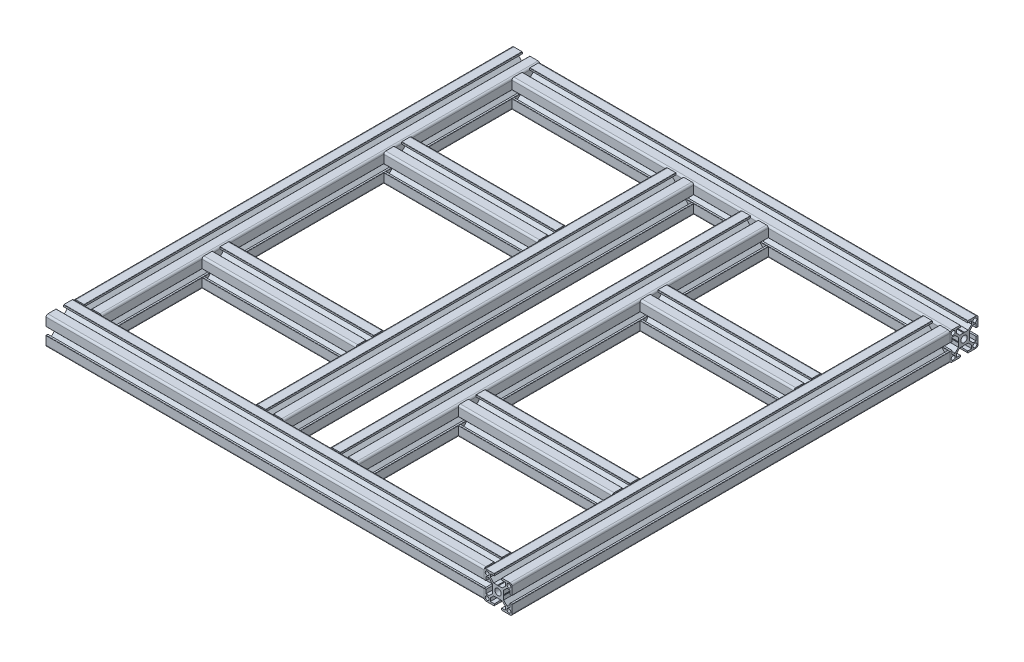
SolidWorks part; units mm, degrees
ref_plane "Front Plane" through (0, 0, 0) normal (0, 0, 1) x (1, 0, 0)
ref_plane "Top Plane" through (0, 0, 0) normal (0, 1, 0) x (1, 0, 0)
ref_plane "Right Plane" through (0, 0, 0) normal (1, 0, 0) x (0, 0, -1)
sketch "Sketch1" plane through (0, 0, 0) normal (0, 1, 0) x (1, 0, 0)
  line L0 (-40, 235) -> (-40, -235)
  line L1 (-235, 235) -> (235, 235)
  line L2 (-235, 235) -> (-235, -235)
  line L3 (-235, -235) -> (235, -235)
  line L4 (235, 235) -> (235, -235)
  line L5 (-235, 235) -> (235, -235) construction
  line L6 (-235, -235) -> (235, 235) construction
  line L7 (40, 235) -> (40, -235)
  line L8 (-235, 97.5) -> (-40, 97.5)
  line L9 (-235, -97.5) -> (-40, -97.5)
  line L11 (40, 97.5) -> (235, 97.5)
  line L14 (40, -97.5) -> (235, -97.5)
  point P0 (0, 0)
  point P15 (-235, 0)
  point P18 (0, 0)
  point P19 (0, 0)
  dimension "D1" = 470
  dimension "D2" = 195
  dimension "D3" = 195
  dimension "D4" = 97.5
  dimension "D5" = 195
other "30xs6 30X30S6(1)" corner treatment butt1
ref_plane "Plane1" through (-235, 0, -235) normal (1, 0, 0) x (0, 0, -1)
sketch "草图1" plane through (-235, 0, -235) normal (1, 0, 0) x (0, 0, -1)
  line L0 (-14.7, 4) -> (-13, 4)
  line L1 (-13, 4) -> (-13, 8.25)
  line L2 (-13, 8.25) -> (-9.6642, 8.25)
  line L3 (-9.6642, 8.25) -> (-6, 4.5858)
  line L4 (-6, 4.5858) -> (-6, 0.5196)
  line L5 (-6, 0.5196) -> (-5.7, 0)
  line L6 (-5.7, 0) -> (-6, -0.5196)
  line L7 (-6, -0.5196) -> (-6, -4.5858)
  line L8 (-6, -4.5858) -> (-9.6642, -8.25)
  line L9 (-9.6642, -8.25) -> (-13, -8.25)
  line L10 (-13, -8.25) -> (-13, -4)
  line L11 (-13, -4) -> (-14.7, -4)
  line L12 (-15, -4.3) -> (-15, -13)
  line L13 (-13, -15) -> (-4.3, -15)
  line L14 (-4, -14.7) -> (-4, -13)
  line L15 (-4, -13) -> (-8.25, -13)
  line L16 (-8.25, -13) -> (-8.25, -9.6642)
  line L17 (-8.25, -9.6642) -> (-4.5858, -6)
  line L18 (-4.5858, -6) -> (-0.5196, -6)
  line L19 (-0.5196, -6) -> (0, -5.7)
  line L20 (0, -5.7) -> (0.5196, -6)
  line L21 (0.5196, -6) -> (4.5858, -6)
  line L22 (4.5858, -6) -> (8.25, -9.6642)
  line L23 (8.25, -9.6642) -> (8.25, -13)
  line L24 (8.25, -13) -> (4, -13)
  line L25 (4, -13) -> (4, -14.7)
  line L26 (4.3, -15) -> (13, -15)
  line L27 (15, -13) -> (15, -4.3)
  line L28 (14.7, -4) -> (13, -4)
  line L29 (13, -4) -> (13, -8.25)
  line L30 (13, -8.25) -> (9.6642, -8.25)
  line L31 (9.6642, -8.25) -> (6, -4.5858)
  line L32 (6, -4.5858) -> (6, -0.5196)
  line L33 (6, -0.5196) -> (5.7, 0)
  line L34 (5.7, 0) -> (6, 0.5196)
  line L35 (6, 0.5196) -> (6, 4.5858)
  line L36 (6, 4.5858) -> (9.6642, 8.25)
  line L37 (9.6642, 8.25) -> (13, 8.25)
  line L38 (13, 8.25) -> (13, 4)
  line L39 (13, 4) -> (14.7, 4)
  line L40 (15, 4.3) -> (15, 13)
  line L41 (13, 15) -> (4.3, 15)
  line L42 (4, 14.7) -> (4, 13)
  line L43 (4, 13) -> (8.25, 13)
  line L44 (8.25, 13) -> (8.25, 9.6642)
  line L45 (8.25, 9.6642) -> (4.5858, 6)
  line L46 (4.5858, 6) -> (0.5196, 6)
  line L47 (0.5196, 6) -> (0, 5.7)
  line L48 (0, 5.7) -> (-0.5196, 6)
  line L49 (-0.5196, 6) -> (-4.5858, 6)
  line L50 (-4.5858, 6) -> (-8.25, 9.6642)
  line L51 (-8.25, 9.6642) -> (-8.25, 13)
  line L52 (-8.25, 13) -> (-4, 13)
  line L53 (-4, 13) -> (-4, 14.7)
  line L54 (-4.3, 15) -> (-13, 15)
  line L55 (-15, 13) -> (-15, 4.3)
  arc A0 (-15, 4.3) -> (-14.7, 4) centre (-14.7, 4.3) ccw
  arc A1 (-14.7, -4) -> (-15, -4.3) centre (-14.7, -4.3) ccw
  arc A2 (-15, -13) -> (-13, -15) centre (-13, -13) ccw
  arc A3 (-4.3, -15) -> (-4, -14.7) centre (-4.3, -14.7) ccw
  arc A4 (4, -14.7) -> (4.3, -15) centre (4.3, -14.7) ccw
  arc A5 (13, -15) -> (15, -13) centre (13, -13) ccw
  arc A6 (15, -4.3) -> (14.7, -4) centre (14.7, -4.3) ccw
  arc A7 (14.7, 4) -> (15, 4.3) centre (14.7, 4.3) ccw
  arc A8 (15, 13) -> (13, 15) centre (13, 13) ccw
  arc A9 (4.3, 15) -> (4, 14.7) centre (4.3, 14.7) ccw
  arc A10 (-4, 14.7) -> (-4.3, 15) centre (-4.3, 14.7) ccw
  arc A11 (-13, 15) -> (-15, 13) centre (-13, 13) ccw
  circle A12 centre (11.625, 11.625) radius 2.1
  circle A13 centre (11.625, -11.625) radius 2.1
  circle A14 centre (0, 0) radius 3.4
  circle A15 centre (-11.625, -11.625) radius 2.1
  circle A16 centre (-11.625, 11.625) radius 2.1
  point P90 (-15, 15)
  point P91 (-0.2598, 14.9121)
  point P92 (15, 15)
  point P93 (15, 0)
  point P94 (15, -15)
  point P95 (0.2598, -15)
  point P96 (-15, -15)
  point P97 (-15, 0)
  point P98 (0, 0)
